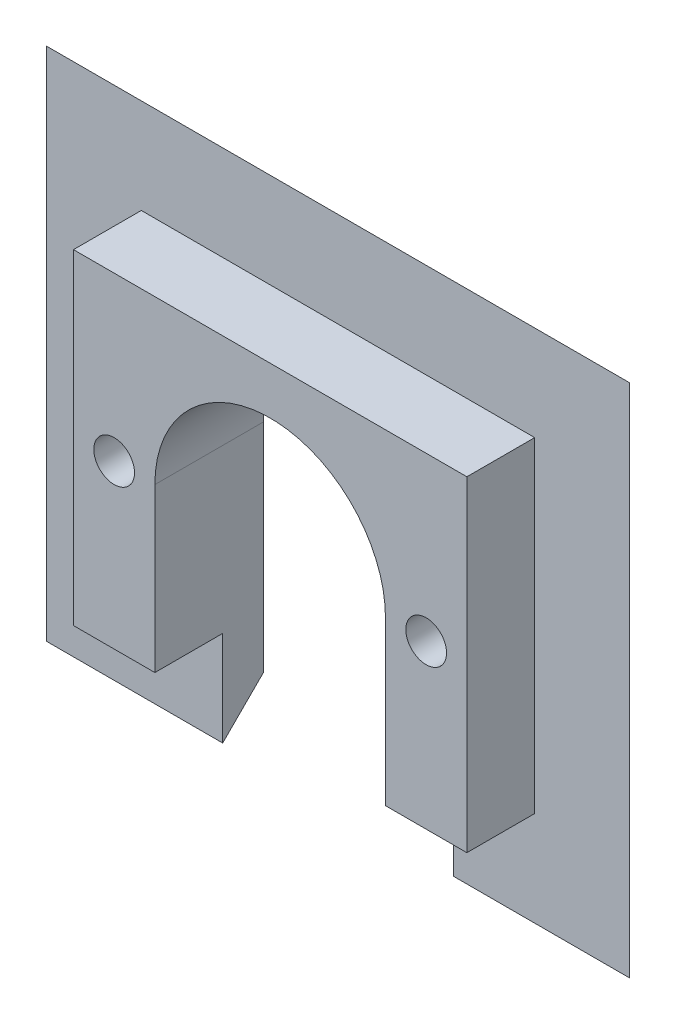
SolidWorks part; units mm, degrees
ref_plane "正面" through (0, 0, 0) normal (0, 0, 1) x (1, 0, 0)
ref_plane "平面" through (0, 0, 0) normal (0, 1, 0) x (1, 0, 0)
ref_plane "右側面" through (0, 0, 0) normal (1, 0, 0) x (0, 0, -1)
sketch "ｽｹｯﾁ1" plane through (0, 0, 0) normal (0, 0, 1) x (1, 0, 0)
  line L0 (8.5, 0) -> (8.5, -12)
  line L1 (-14.5, -12) -> (14.5, -12)
  line L2 (-14.5, -12) -> (-14.5, 12)
  line L3 (-14.5, 12) -> (14.5, 12)
  line L4 (14.5, -12) -> (14.5, 12)
  line L5 (-14.5, -12) -> (14.5, 12) construction
  line L6 (-14.5, 12) -> (14.5, -12) construction
  line L7 (8.5, -12) -> (8.5, 0)
  line L8 (-8.5, 0) -> (-8.5, -12)
  line L9 (-8.5, -12) -> (-8.5, 0)
  circle A0 centre (0, 0) radius 8.5
  point P0 (0, 0)
  dimension "D3" = 17
  dimension "D1" = 29
  dimension "D2" = 24
extrude "ﾎﾞｽ - 押し出し1" add sketch "ｽｹｯﾁ1" along normal blind 5 contours A0 L0 L1 L4 L3 L2 L8 region at (0, 8.8764, 0)
sketch "ｽｹｯﾁ2" plane through (0, 0, 0) normal (0, 0, -1) x (-1, 0, 0)
  line L0 (8.5, -12) -> (8.5, -19)
  line L1 (8.5, -19) -> (21.5, -19)
  line L2 (21.5, -19) -> (21.5, 19)
  line L3 (21.5, 19) -> (-21.5, 19)
  line L4 (-21.5, 19) -> (-21.5, -19)
  line L5 (-21.5, -19) -> (-8.5, -19)
  line L6 (-8.5, -19) -> (-8.5, -12)
  line L7 (14.5, -12) -> (14.5, 12) construction
  line L8 (14.5, 12) -> (-14.5, 12) construction
  line L9 (-14.5, -12) -> (-14.5, 12) construction
  line L10 (-8.5, -12) -> (-14.5, -12) construction
  line L11 (-8.5, -12) -> (-8.5, 0)
  line L12 (8.5, -12) -> (8.5, 0)
  arc A0 (-8.5, 0) -> (8.5, 0) centre (0, 0) cw
  dimension "D1" = 7
  dimension "D2" = 7
  dimension "D3" = 7
  dimension "D4" = 7
  dimension "D5" = 7
extrude "ﾎﾞｽ - 押し出し2" add sketch "ｽｹｯﾁ2" along normal blind 3
sketch "ｽｹｯﾁ3" plane through (0, 0, 5) normal (0, 0, 1) x (1, 0, 0)
  line L0 (14.5, -12) -> (14.5, 12) construction
  line L1 (-14.5, -12) -> (-14.5, 12) construction
  circle A0 centre (11.5, 0) radius 1.5
  circle A1 centre (-11.5, 0) radius 1.5
  dimension "D1" = 3
  dimension "D2" = 3
  dimension "D3" = 3
  dimension "D4" = 3
extrude "ｶｯﾄ - 押し出し1" cut sketch "ｽｹｯﾁ3" against normal through all
chamfer "面取り1" distance 3 angle 45 5 edges at (15, -19, -3) (21.5, 0, -3) (0, 19, -3) (-21.5, 0, -3) (-15, -19, -3)
